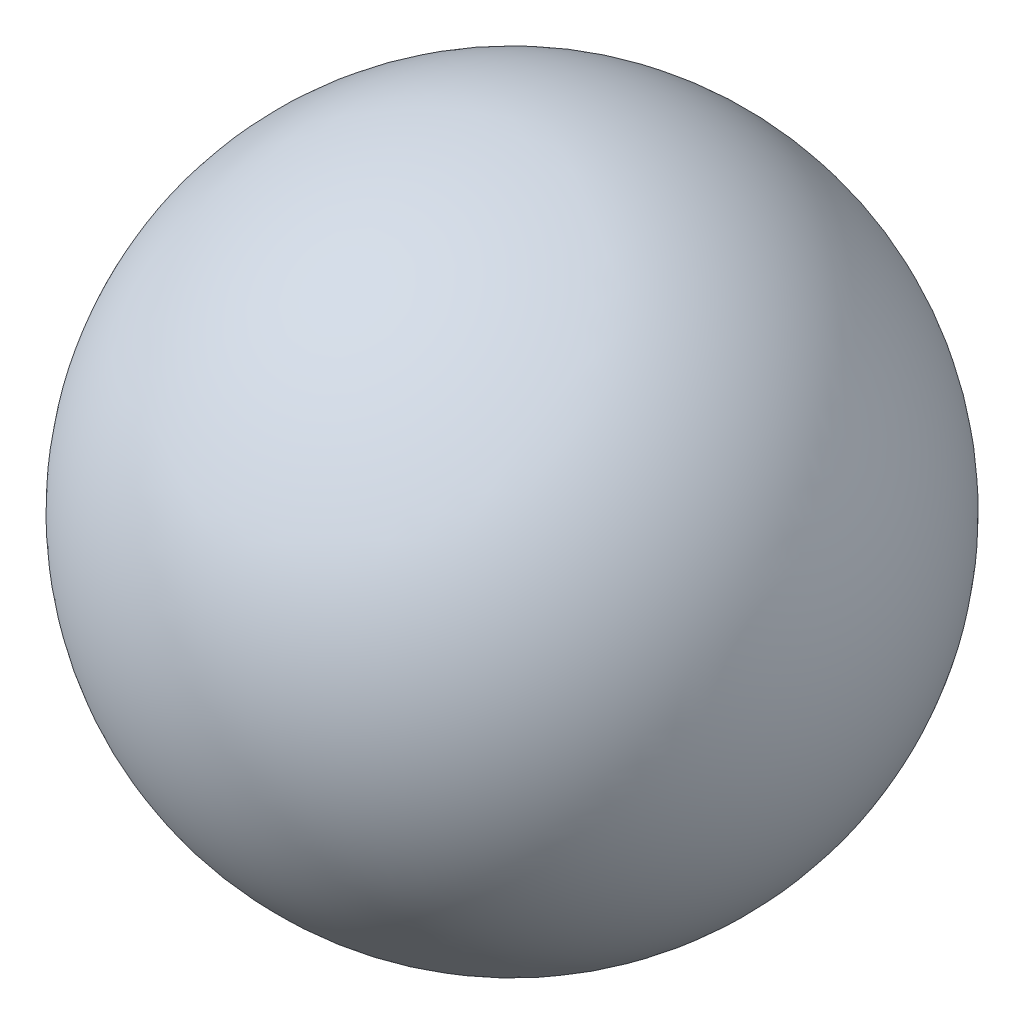
SolidWorks part; units mm, degrees
ref_plane "Front Plane" through (0, 0, 0) normal (0, 0, 1) x (1, 0, 0)
ref_plane "Top Plane" through (0, 0, 0) normal (0, 1, 0) x (1, 0, 0)
ref_plane "Right Plane" through (0, 0, 0) normal (1, 0, 0) x (0, 0, -1)
sketch "Sketch2" plane through (0, 0, 0) normal (0, 0, 1) x (1, 0, 0)
  line L0 (904.5329, 0) -> (-904.5329, 0)
  arc A0 (904.5329, 0) -> (-904.5329, 0) centre (0, 0) ccw
  dimension "D1" = 1809.0658
revolve "Revolve1" add sketch "Sketch2" angle 360 about L0
